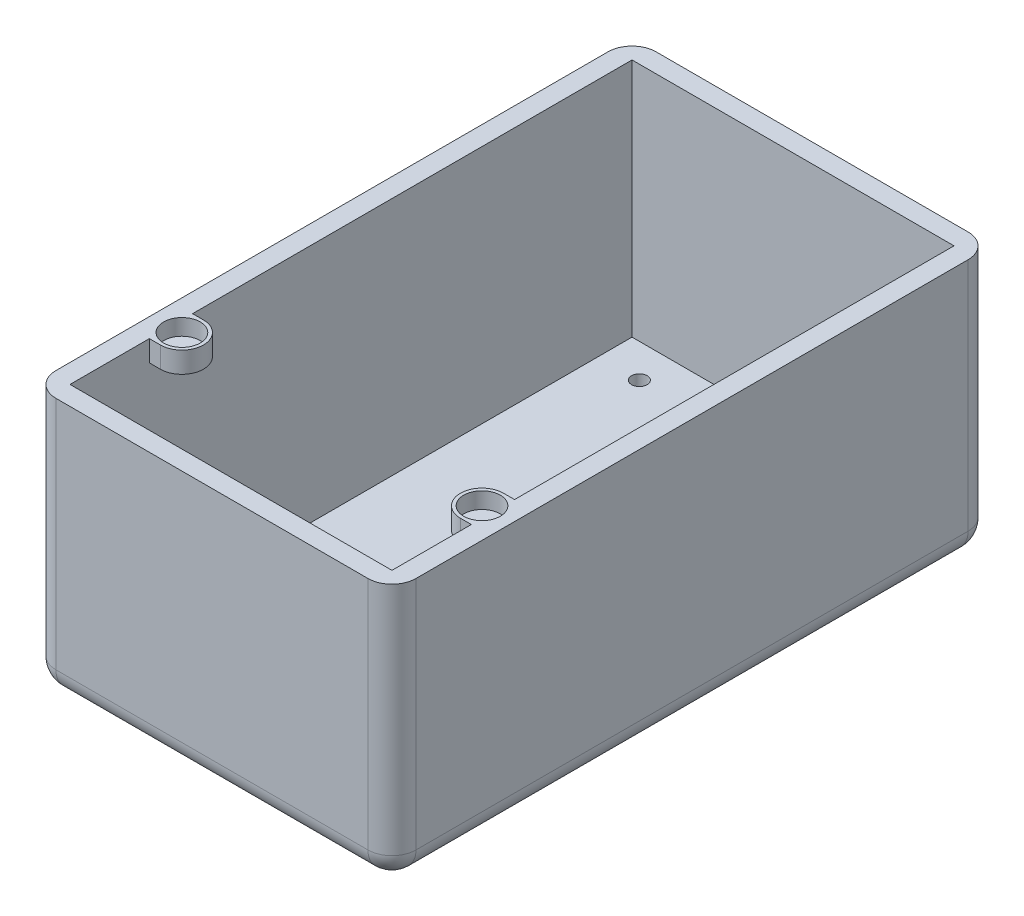
SolidWorks part; units mm, degrees
ref_plane "Front Plane" through (0, 0, 0) normal (0, 0, 1) x (1, 0, 0)
ref_plane "Top Plane" through (0, 0, 0) normal (0, 1, 0) x (1, 0, 0)
ref_plane "Right Plane" through (0, 0, 0) normal (1, 0, 0) x (0, 0, -1)
sketch "Sketch1" plane through (0, 0, 0) normal (0, 1, 0) x (1, 0, 0)
  line L1 (-30, 50) -> (30, 50)
  line L2 (-30, 50) -> (-30, -50)
  line L3 (-30, -50) -> (30, -50)
  line L4 (30, 50) -> (30, -50)
  line L5 (-30, 50) -> (30, -50) construction
  line L6 (-30, -50) -> (30, 50) construction
  line L7 (-26.825, 46.825) -> (26.825, 46.825)
  line L8 (-26.825, 46.825) -> (-26.825, -46.825)
  line L9 (-26.825, -46.825) -> (26.825, -46.825)
  line L10 (26.825, 46.825) -> (26.825, -46.825)
  line L11 (-26.825, 46.825) -> (26.825, -46.825) construction
  line L12 (-26.825, -46.825) -> (26.825, 46.825) construction
  point P0 (0, 0)
  point P6 (0, 0)
  dimension "D1" = 3.175
  dimension "D2" = 3.175
  dimension "D3" = 100
  dimension "D4" = 60
extrude "Boss-Extrude1" add sketch "Sketch1" along normal blind 40
sketch "Sketch2" plane through (0, 0, 0) normal (0, -1, 0) x (1, 0, 0)
  line L1 (30, -50) -> (-30, -50)
  line L2 (30, -50) -> (30, 50)
  line L3 (30, 50) -> (-30, 50)
  line L4 (-30, -50) -> (-30, 50)
extrude "Boss-Extrude2" add sketch "Sketch2" along normal blind 3.175
fillet "Fillet1" radius 4 8 edges at (30, 18.4125, 50) (30, 18.4125, -50) (-30, 18.4125, -50) (-30, 18.4125, 50) (0, -3.175, 50) (-30, -3.175, 0) (0, -3.175, -50) (30, -3.175, 0)
sketch "Sketch3" plane through (0, 0, 0) normal (0, 1, 0) x (1, 0, 0)
  line L0 (-26.825, -46.825) -> (26.825, -46.825) construction
  line L1 (-20, 41.225) -> (3.05, 41.225) construction
  line L2 (-20, 41.225) -> (-20, -16.825) construction
  line L3 (-20, -16.825) -> (3.05, -16.825) construction
  line L4 (3.05, 41.225) -> (3.05, -16.825) construction
  line L6 (-26, -46) -> (-26, 46) construction
  circle A0 centre (-20, 41.225) radius 1.3
  circle A1 centre (3.05, 41.225) radius 1.3
  circle A2 centre (3.05, -16.825) radius 1.3
  circle A3 centre (-20, -16.825) radius 1.3
  dimension "D2" = 2.6
  dimension "D1" = 58.05
  dimension "D3" = 23.05
  dimension "D4" = 30
  dimension "D5" = 6
extrude "Cut-Extrude1" cut sketch "Sketch3" against normal up to surface (3.175 mm away) up to face at (0, -3.175, 0)
sketch "Sketch4" plane through (0, 40, 0) normal (0, 1, 0) x (1, 0, 0)
  line L0 (-25, -26.4) -> (-26.825, -26.4)
  line L1 (-26.825, 46.825) -> (-26.825, -46.825) construction
  line L2 (-26.825, -26.4) -> (-26.825, -33.6)
  line L3 (-26.825, -33.6) -> (-25, -33.6)
  line L4 (0, -50) -> (0, 50) construction
  line L5 (-26, -50) -> (26, -50) construction
  line L6 (26, 50) -> (-26, 50) construction
  line L7 (-30, 46) -> (-30, -46) construction
  line L8 (26.825, -33.6) -> (25, -33.6)
  line L9 (26.825, -26.4) -> (26.825, -33.6)
  line L10 (25, -26.4) -> (26.825, -26.4)
  arc A0 (-25, -33.6) -> (-25, -26.4) centre (-25, -30) ccw
  arc A1 (25, -33.6) -> (25, -26.4) centre (25, -30) cw
  dimension "D1" = 7.2
  dimension "D2" = 5
  dimension "D3" = 20
extrude "Boss-Extrude3" add sketch "Sketch4" against normal blind 3.5
sketch "Sketch5" plane through (0, 40, 0) normal (0, 1, 0) x (1, 0, 0)
  line L0 (0, 50) -> (0, -50) construction
  line L1 (26, 50) -> (-26, 50) construction
  line L2 (-26, -50) -> (26, -50) construction
  circle A0 centre (-25, -30) radius 3.05
  circle A1 centre (25, -30) radius 3.05
  dimension "D1" = 6.1
extrude "Cut-Extrude2" cut sketch "Sketch5" against normal blind 2.7
